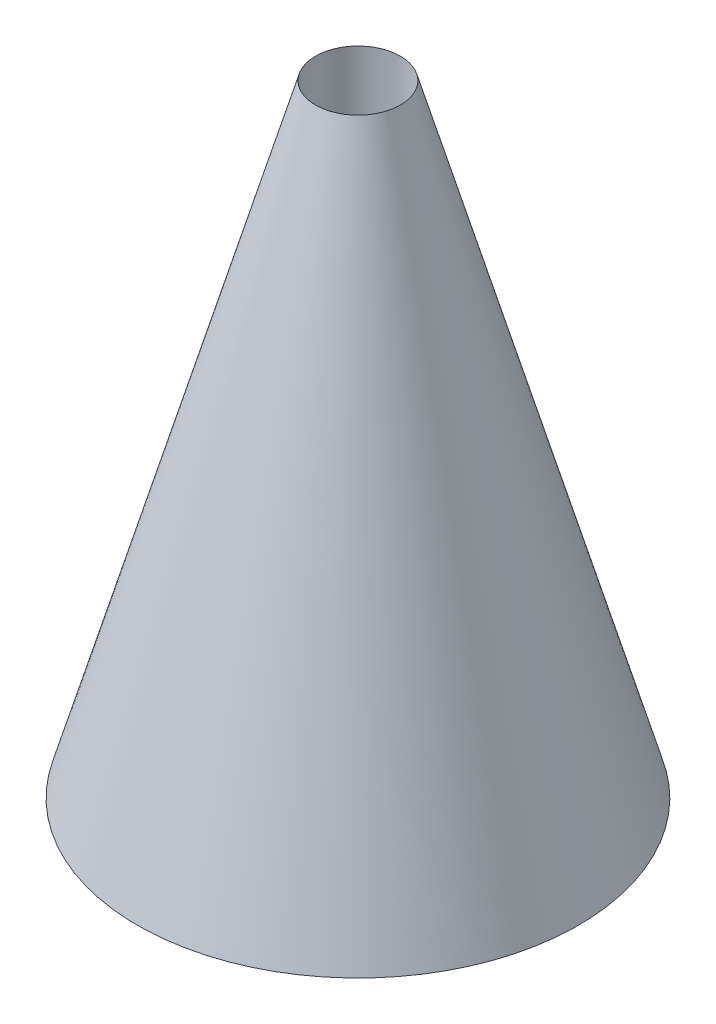
SolidWorks part; units mm, degrees
ref_plane "Front Plane" through (0, 0, 0) normal (0, 0, 1) x (1, 0, 0)
ref_plane "Top Plane" through (0, 0, 0) normal (0, 1, 0) x (1, 0, 0)
ref_plane "Right Plane" through (0, 0, 0) normal (1, 0, 0) x (0, 0, -1)
sketch "Sketch1" plane through (0, 0, 0) normal (0, 0, 1) x (1, 0, 0)
  line L0 (39.6, 0) -> (39.6, 80) construction
  line L1 (0, 0) -> (0, 589.6776) construction
  line L2 (38.1, 0) -> (38.1, 80) construction
  line L3 (0, 330) -> (0, 325.1029) construction
  line L4 (0, 0) -> (163.2597, 0) construction
  line L5 (38.1, 0) -> (39.6, 0) construction
  line L6 (0, 325.1029) -> (0, 279.7588)
  line L7 (0, 279.7588) -> (13, 279.7588)
  line L8 (13, 279.7588) -> (0, 325.1029)
  spline S0 degree 4 poles (-8.2172, 354.0002) (-8.1494, 353.8119) (-8.0142, 353.436) (-7.7464, 352.6901) (-7.2062, 351.1775) (-6.4789, 349.1293) (-5.5446, 346.4662) (-4.5162, 343.5025) (-3.4692, 340.4406) (-2.4903, 337.5478) (-1.5626, 334.7623) (-0.909, 332.7858) (-0.1595, 330.4915) (0.1448, 329.5553) (0.8619, 327.337) (1.48, 325.4029) (2.3193, 322.756) (3.4273, 319.2089) (4.7721, 314.8325) (6.2871, 309.7858) (7.9895, 303.961) (9.4331, 298.8777) (10.6481, 294.4982) (11.6396, 290.8519) (12.4234, 287.9276) (13.3884, 284.2716) (14.5251, 279.877) (16.1886, 273.2758) (17.9639, 265.9224) (19.6656, 258.5519) (21.6195, 249.6874) (23.4848, 240.8038) (25.2393, 231.8974) (26.8825, 222.97) (28.4366, 214.0267) (29.9015, 205.0683) (31.2545, 196.0922) (32.4955, 187.1001) (33.6468, 178.0961) (34.7082, 169.081) (35.6572, 160.0532) (36.4935, 151.0145) (37.1152, 143.4756) (37.5675, 137.4412) (37.9746, 131.4031) (38.3366, 125.3629) (38.6137, 120.0744) (38.823, 115.5417) (38.9786, 111.7609) (39.0917, 108.7406) (39.219, 104.9539) (39.3275, 101.1857) (39.417, 97.3848) (39.4878, 93.6314) (39.533, 90.5579) (39.567, 87.6237) (39.5868, 84.8177) (39.5967, 82.8056) (39.6003, 80.4721) (39.6002, 79.4963) (39.5965, 77.113) (39.5861, 75.0596) (39.5652, 72.1674) (39.5293, 69.1569) (39.4812, 65.9684) (39.4209, 62.8765) (39.3573, 60.0957) (39.3002, 57.9538) (39.2552, 56.3714) (39.2317, 55.5905) (39.2197, 55.197) (39.2136, 54.9998) knots 0 0 0 0 0 0.002619 0.005238 0.010476 0.020951 0.031427 0.041903 0.052253 0.062603 0.072953 0.078128 0.083304 0.088271 0.093239 0.103175 0.11311 0.123046 0.142917 0.162788 0.18266 0.202531 0.212466 0.222402 0.232338 0.242273 0.262144 0.282016 0.321758 0.341629 0.3615 0.401243 0.440985 0.460857 0.480728 0.52047 0.560213 0.580084 0.599955 0.639697 0.67944 0.699311 0.719182 0.739053 0.758925 0.778796 0.798667 0.808603 0.818538 0.828474 0.838409 0.858281 0.868216 0.878152 0.888087 0.898023 0.907959 0.912926 0.917894 0.922995 0.928095 0.938296 0.948496 0.958697 0.969023 0.979348 0.989674 0.994837 0.997419 1 1 1 1 1 construction
  spline S1 degree 4 poles (0, 330) (0.0976, 329.6998) (0.293, 329.0969) (0.8619, 327.337) (1.48, 325.4029) (2.3193, 322.756) (3.4273, 319.2089) (4.7721, 314.8325) (6.2871, 309.7858) (7.9895, 303.961) (9.4331, 298.8777) (10.6481, 294.4982) (11.6396, 290.8519) (12.4234, 287.9276) (13.3884, 284.2716) (14.5251, 279.877) (16.1886, 273.2758) (17.9639, 265.9224) (19.6656, 258.5519) (21.6195, 249.6874) (23.4848, 240.8038) (25.2393, 231.8974) (26.8825, 222.97) (28.4366, 214.0267) (29.9015, 205.0683) (31.2545, 196.0922) (32.4955, 187.1001) (33.6468, 178.0961) (34.7082, 169.081) (35.6572, 160.0532) (36.4935, 151.0145) (37.1152, 143.4756) (37.5675, 137.4412) (37.9746, 131.4031) (38.3366, 125.3629) (38.6137, 120.0744) (38.823, 115.5417) (38.9786, 111.7609) (39.0917, 108.7406) (39.219, 104.9539) (39.3275, 101.1857) (39.417, 97.3848) (39.4878, 93.6314) (39.533, 90.5579) (39.567, 87.6237) (39.5868, 84.8177) (39.5967, 82.8056) (39.5995, 80.9487) (39.6, 80.3157) (39.6, 80) knots 0.083304 0.083304 0.083304 0.083304 0.083304 0.088271 0.093239 0.103175 0.11311 0.123046 0.142917 0.162788 0.18266 0.202531 0.212466 0.222402 0.232338 0.242273 0.262144 0.282016 0.321758 0.341629 0.3615 0.401243 0.440985 0.460857 0.480728 0.52047 0.560213 0.580084 0.599955 0.639697 0.67944 0.699311 0.719182 0.739053 0.758925 0.778796 0.798667 0.808603 0.818538 0.828474 0.838409 0.858281 0.868216 0.878152 0.888087 0.898023 0.907959 0.912926 0.917894 0.917894 0.917894 0.917894 0.917894 construction
  spline S2 degree 1 poles (-1.4266, 329.5364) (38.1, 80) knots 0 0 1 1 construction
  spline S3 degree 3 poles (-1.4266, 329.5364) (-1.383, 329.4024) (-1.2989, 329.1432) (-1.1081, 328.554) (-0.8243, 327.6757) (-0.4974, 326.66) (-0.2579, 325.9116) (-0.0684, 325.3176) (0.0486, 324.9503) (0.2006, 324.4721) (0.5038, 323.5167) (1.1954, 321.326) (2.1624, 318.219) (3.7193, 313.134) (5.5999, 306.8222) (8.7328, 295.9212) (11.3411, 286.2588) (13.9564, 276.0163) (20.0951, 251.1019) (28.9783, 206.4522) (34.5733, 159.1795) (36.7511, 127.5431) (37.3996, 114.3427) (37.7627, 103.7831) (37.9087, 97.8304) (37.9816, 93.8801) (38.0132, 91.8818) (38.04, 89.9069) (38.0619, 87.9504) (38.0761, 86.2546) (38.085, 84.9378) (38.0905, 83.982) (38.0947, 83.024) (38.0978, 81.9582) (38.0993, 81.033) (38.0999, 80.4133) (38.1, 80.1409) (38.1, 80) knots 0.083304 0.083304 0.083304 0.083304 0.084934 0.086564 0.089824 0.093084 0.096344 0.097819 0.099449 0.100264 0.102864 0.109385 0.122425 0.135466 0.161546 0.187627 0.24731 0.260351 0.291951 0.500599 0.709247 0.761408 0.81357 0.839651 0.865732 0.872253 0.878773 0.885293 0.891813 0.898334 0.901594 0.904854 0.908114 0.911374 0.914634 0.916264 0.917894 0.917894 0.917894 0.917894 only from (0, 325.1029) to (38.1, 80) construction
  dimension "D1" = 80
  dimension "D2" = 39.6
  dimension "D4" = 13
  dimension "D3" = 1.5
revolve "Revolve1" add sketch "Sketch1" angle 360 about L1
sketch "Sketch2" plane through (0, 279.7588, 0) normal (0, -1, 0) x (1, 0, 0)
  circle A0 centre (0, 0) radius 2.5
  dimension "D1" = 5
extrude "Cut-Extrude1" cut sketch "Sketch2" against normal through all
sketch "Sketch4" plane through (0, 0, 0) normal (0, 0, 1) x (1, 0, 0)
  line L0 (0, 279.7588) -> (0, 328.1412) construction
  line L1 (-13, 279.7588) -> (13, 279.7588) construction
  line L2 (13, 279.7588) -> (2.5, 316.3828) construction
  line L3 (13, 279.7588) -> (2.5, 316.3828)
  line L4 (2.5, 316.3828) -> (0, 321.4743)
  line L5 (13, 279.7588) -> (11.9597, 279.7588)
  line L6 (11.9597, 279.7588) -> (0, 321.4743)
  line L7 (12.0387, 279.4832) -> (1.5387, 316.1073) construction
  point P9 (0, 0)
  dimension "D1" = 1
revolve "Cut-Revolve1" cut sketch "Sketch4" angle 360 about L0 rebuild error yes
